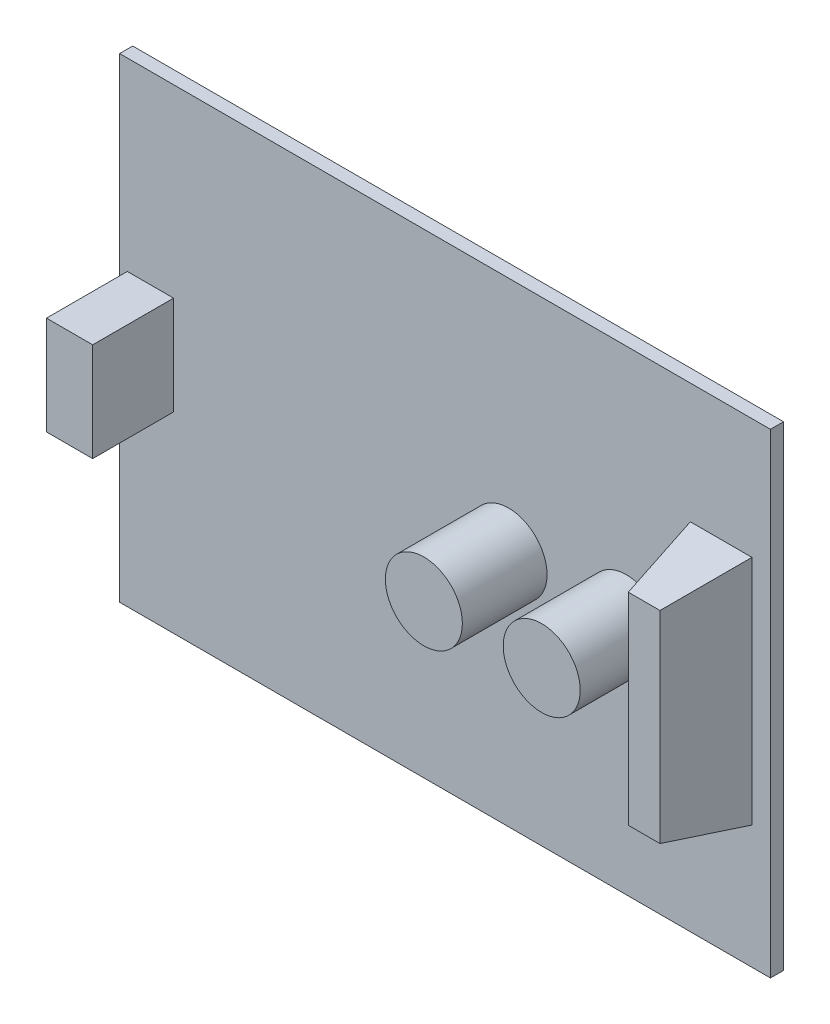
SolidWorks part; units mm, degrees
ref_plane "Front Plane" through (0, 0, 0) normal (0, 0, 1) x (1, 0, 0)
ref_plane "Top Plane" through (0, 0, 0) normal (0, 1, 0) x (1, 0, 0)
ref_plane "Right Plane" through (0, 0, 0) normal (1, 0, 0) x (0, 0, -1)
sketch "Sketch1" plane through (0, 0, 0) normal (0, 0, 1) x (1, 0, 0)
  line L1 (-31.097, 42.74) -> (53.403, 42.74)
  line L2 (-31.097, 42.74) -> (-31.097, -18.96)
  line L3 (-31.097, -18.96) -> (53.403, -18.96)
  line L4 (53.403, 42.74) -> (53.403, -18.96)
  dimension "D1" = 84.5
  dimension "D2" = 61.7
extrude "Boss-Extrude1" add sketch "Sketch1" along normal blind 1.7
sketch "Sketch2" plane through (0, 0, 1.7) normal (0, 0, 1) x (1, 0, 0)
  line L0 (53.403, -18.96) -> (53.403, 42.74) construction
  line L1 (43.003, 27.14) -> (51.003, 27.14)
  line L2 (43.003, 27.14) -> (43.003, -2.96)
  line L3 (43.003, -2.96) -> (51.003, -2.96)
  line L4 (51.003, 27.14) -> (51.003, -2.96)
  line L5 (53.403, 42.74) -> (-31.097, 42.74) construction
  point P4 (47.003, 27.14)
  dimension "D1" = 30.1
  dimension "D2" = 8
  dimension "D3" = 2.4
  dimension "D4" = 15.6
extrude "Boss-Extrude2" add sketch "Sketch2" along normal blind 10 draft 11
sketch "Sketch3" plane through (0, 0, 1.7) normal (0, 0, 1) x (1, 0, 0)
  line L0 (53.403, 42.74) -> (-31.097, 42.74) construction
  line L3 (53.403, -18.96) -> (53.403, 42.74) construction
  circle A0 centre (19.403, 11.89) radius 5
  point P6 (-31.097, 13.6111)
  dimension "D1" = 10
  dimension "D2" = 30.85
  dimension "D3" = 34
extrude "Boss-Extrude3" add sketch "Sketch3" along normal blind 11
sketch "Sketch4" plane through (0, 0, 1.7) normal (0, 0, 1) x (1, 0, 0)
  line L0 (53.403, -18.96) -> (53.403, 42.74) construction
  line L1 (-31.097, -18.96) -> (53.403, -18.96) construction
  circle A0 centre (34.703, 12.04) radius 5
  dimension "D1" = 10
  dimension "D2" = 18.7
  dimension "D3" = 31
extrude "Boss-Extrude4" add sketch "Sketch4" along normal blind 11
sketch "Sketch5" plane through (0, 0, 1.7) normal (0, 0, 1) x (1, 0, 0)
  line L0 (-31.097, 42.74) -> (-31.097, -18.96) construction
  line L1 (-30.097, 18.74) -> (-24.097, 18.74)
  line L2 (-30.097, 18.74) -> (-30.097, 5.94)
  line L3 (-30.097, 5.94) -> (-24.097, 5.94)
  line L4 (-24.097, 18.74) -> (-24.097, 5.94)
  line L5 (53.403, 42.74) -> (-31.097, 42.74) construction
  point P8 (-27.097, 18.74)
  dimension "D1" = 1
  dimension "D2" = 24
  dimension "D3" = 6
  dimension "D4" = 12.8
extrude "Boss-Extrude5" add sketch "Sketch5" along normal blind 10.5
